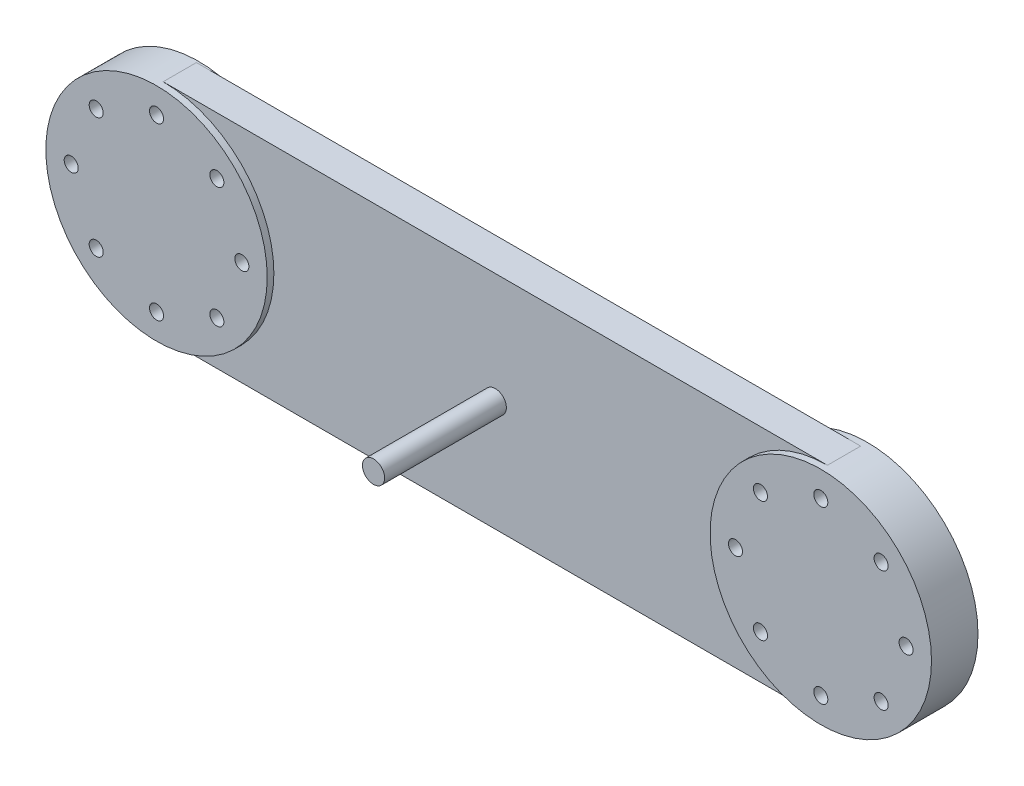
SolidWorks part; units mm, degrees
material "3003 Alloy"
ref_plane "前视基准面" through (0, 0, 0) normal (0, 0, 1) x (1, 0, 0)
ref_plane "上视基准面" through (0, 0, 0) normal (0, 1, 0) x (1, 0, 0)
ref_plane "右视基准面" through (0, 0, 0) normal (1, 0, 0) x (0, 0, -1)
sketch "草图1" plane through (0, 0, 0) normal (0, 0, 1) x (1, 0, 0)
  line L0 (0, 100) -> (-300, 0) construction
  line L5 (0, 0) -> (-300, 0)
  line L6 (0, 0) -> (0, 100)
  line L7 (0, 100) -> (-300, 100)
  line L8 (-300, 0) -> (-300, 100)
  line L9 (-300, 100) -> (0, 0) construction
  line L10 (-300, 50) -> (-250, 50)
  line L11 (-250, 50) -> (-300, 100) construction
  line L12 (-300, 50) -> (-264.6447, 85.3553) construction
  line L13 (-300, 50) -> (-335.3553, 14.6447)
  line L14 (-150, 50) -> (-150, 0)
  line L15 (-264.6447, 85.3553) -> (-335.3553, 85.3553) construction
  line L16 (-264.6447, 85.3553) -> (-264.6447, 14.6447) construction
  line L17 (-264.6447, 14.6447) -> (-335.3553, 14.6447) construction
  line L18 (-335.3553, 85.3553) -> (-335.3553, 14.6447) construction
  line L19 (-150, 0) -> (-150, 100) construction
  line L20 (6.25, 50) -> (8.25, 50)
  line L21 (6.25, 50) -> (8.25, 50)
  line L22 (6.25, 47.9959) -> (6.25, 52.0041)
  line L23 (8.25, 47.9959) -> (8.25, 52.0041)
  line L24 (6.25, 52.0041) -> (8.25, 52.0041)
  line L25 (6.25, 52.0041) -> (5.92, 52.0041)
  line L26 (6.25, 52.0041) -> (6.25, 50)
  line L27 (6.25, 52.0041) -> (6.25, 47.9959)
  line L28 (6.25, 52.0041) -> (5.137, 52.0041)
  line L29 (6.25, 50) -> (5.137, 50)
  line L30 (5.137, 52.0041) -> (5.137, 47.9959)
  line L31 (6.25, 47.9959) -> (5.137, 47.9959)
  line L32 (6.25, 47.9959) -> (8.25, 47.9959)
  circle A6 centre (0, 50) radius 50
  circle A7 centre (0, 50) radius 25
  circle A8 centre (-300, 50) radius 50
  circle A9 centre (-300, 50) radius 25
  circle A12 centre (-150, 50) radius 5
  circle A14 centre (-261.4697, 50) radius 3.175
  circle A23 centre (-38.5303, 50) radius 3.175
  circle A30 centre (-272.7549, 22.7549) radius 3.175
  circle A31 centre (-300, 11.4697) radius 3.175
  circle A32 centre (-327.2451, 22.7549) radius 3.175
  circle A33 centre (-338.5303, 50) radius 3.175
  circle A34 centre (-327.2451, 77.2451) radius 3.175
  circle A35 centre (-300, 88.5303) radius 3.175
  circle A36 centre (-272.7549, 77.2451) radius 3.175
  circle A37 centre (-27.2451, 77.2451) radius 3.175
  circle A38 centre (-27.2451, 77.2451) radius 3.175
  circle A39 centre (0, 88.5303) radius 3.175
  circle A40 centre (27.2451, 77.2451) radius 3.175
  circle A41 centre (38.5303, 50) radius 3.175
  circle A42 centre (27.2451, 22.7549) radius 3.175
  circle A43 centre (0, 11.4697) radius 3.175
  circle A44 centre (-27.2451, 22.7549) radius 3.175
  circle A45 centre (0, 50) radius 6.25
  circle A46 centre (0, 50) radius 9.525
  point P70 (-300, 50)
  point P87 (0, 50)
  dimension "D1" = 100
  dimension "D2" = 300
  dimension "D3" = 50
  dimension "D4" = 50
  dimension "D5" = 10
  dimension "D6" = 2
  dimension "D7" = 6.35
  dimension "D8" = 12.5
  dimension "D9" = 19.05
extrude "凸台-拉伸18" add sketch "草图1" along normal blind 13 contours A8 | A6
extrude "凸台-拉伸21" add sketch "草图1<28>" along normal blind 15 contours L5 L8 L7 L6
sketch "草图1<28>" plane through (0, 0, 0) normal (0, 0, 1) x (1, 0, 0) same geometry as "草图1"
extrude "凸台-拉伸22" add sketch "草图1<30>" along normal blind 70 contours A12
sketch "草图1<30>" plane through (0, 0, 0) normal (0, 0, 1) x (1, 0, 0) same geometry as "草图1"
extrude "切除-拉伸2" cut sketch "草图1<31>" along normal blind 41 contours A8
sketch "草图1<31>" plane through (0, 0, 0) normal (0, 0, 1) x (1, 0, 0) same geometry as "草图1"
extrude "凸台-拉伸23" add sketch "草图1<32>" along normal blind 18 and the other way blind 1 contours A8
sketch "草图1<32>" plane through (0, 0, 0) normal (0, 0, 1) x (1, 0, 0) same geometry as "草图1"
extrude "切除-拉伸5" cut sketch "草图1<35>" against normal blind 69 and the other way blind 130 contours A14
sketch "草图1<35>" plane through (0, 0, 0) normal (0, 0, 1) x (1, 0, 0) same geometry as "草图1"
extrude "切除-拉伸6" cut sketch "草图1<36>" along normal blind 34 contours A6
sketch "草图1<36>" plane through (0, 0, 0) normal (0, 0, 1) x (1, 0, 0) same geometry as "草图1"
extrude "凸台-拉伸24" add sketch "草图1<37>" against normal blind 3 and the other way blind 18 contours A6
sketch "草图1<37>" plane through (0, 0, 0) normal (0, 0, 1) x (1, 0, 0) same geometry as "草图1"
extrude "切除-拉伸7" cut sketch "草图1<41>" along normal blind 87 and the other way blind 98 contours A36 | L8 A35 | L8 A35 | A34 | A33 | L13 A32 | L8 A31 | A30 | L10 A14 | L10 A14 | A44 | A23 | A37 | A39 L6 | A39 L6 | A40 | A42 | A41 | A43 L6 | A43 L6 | A32 | A31 | A43 region at (-1.3475, 11.4697, 0) region at (1.3475, 11.4697, 0) region at (1.3475, 88.5303, 0) region at (-1.3475, 88.5303, 0) region at (-298.6525, 11.4697, 0) region at (-298.6525, 88.5303, 0) region at (-301.3475, 88.5303, 0) region at (-326.2922, 21.8021, 0) region at (-261.4697, 48.6525, 0) region at (-261.4697, 51.3475, 0) region at (-38.5303, 50, 0) region at (-272.7549, 22.7549, 0) region at (-338.5303, 50, 0) region at (-327.2451, 77.2451, 0) region at (-272.7549, 77.2451, 0) region at (-27.2451, 77.2451, 0) region at (27.2451, 77.2451, 0) region at (38.5303, 50, 0) region at (27.2451, 22.7549, 0) region at (-27.2451, 22.7549, 0)
sketch "草图1<41>" plane through (0, 0, 0) normal (0, 0, 1) x (1, 0, 0) same geometry as "草图1"
sketch "Sketch1" plane through (0, 0, -3) normal (0, 0, -1) x (-1, 0, 0)
  line L0 (-50, 50) -> (50, 50) construction
  line L1 (0, 0) -> (0, 100) construction
  circle A0 centre (0, 50) radius 50 construction
  arc A1 (0, 0) -> (0, 100) centre (0, 50) ccw construction
  point P11 (0, 50)
ref_point "RotatioanAxixCentre"
sketch "Sketch2" plane through (0, 100, 0) normal (0, 1, 0) x (1, 0, 0)
  line L0 (0, -18) -> (0, 3)
  line L2 (50, 3) -> (-50, 3) construction
  point P3 (0, -7.5)
  dimension "D1" = 10.5
